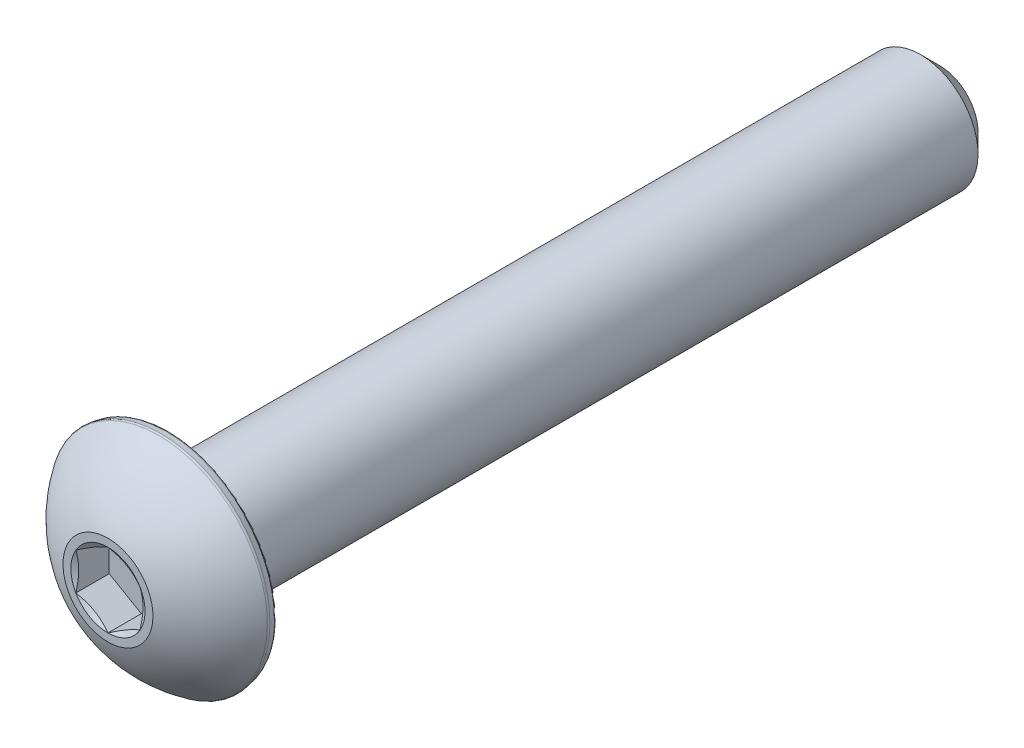
SolidWorks part; units mm, degrees
material "Cast Alloy Steel"
ref_plane "Front Plane" through (0, 0, 0) normal (0, 0, 1) x (1, 0, 0)
ref_plane "Top Plane" through (0, 0, 0) normal (0, 1, 0) x (1, 0, 0)
ref_plane "Right Plane" through (0, 0, 0) normal (1, 0, 0) x (0, 0, -1)
sketch "Sketch1" plane through (0, 0, 0) normal (1, 0, 0) x (0, 0, -1)
  line L0 (0, 0) -> (19.05, 0) construction
  line L1 (19.05, 1.4224) -> (19.05, -1.4224) construction
  line L2 (0, 0) -> (-1.4986, 0) construction
  line L3 (0, 2.7051) -> (0, -2.7051) construction
  line L4 (-1.4986, 0.7937) -> (-1.4986, -0.7937) construction
  line L5 (19.0103, 1.4911) -> (19.6453, 1.4911) construction
  line L6 (19.6453, 1.4911) -> (19.3278, 0.9412) construction
  line L7 (19.3278, 0.9412) -> (19.0103, 1.4911) construction
  line L8 (19.0302, 1.4568) -> (19.6255, 1.4568) construction
  line L9 (19.05, 1.4224) -> (19.6056, 1.4224) construction
  line L10 (19.2881, 1.01) -> (19.3675, 1.01) construction
  line L11 (19.3278, 1.01) -> (19.3278, 0.9412) construction
  line L12 (19.3278, 1.4224) -> (19.3278, 1.4911) construction
  point P5 (19.05, 0)
  point P10 (-1.4986, 0)
  point P13 (0, 0)
  point P18 (17.4625, -1.4224)
  point P25 (19.3278, 1.4568)
  dimension "Screw Size Decimal Equivalent" = 2.8448
  dimension "Length" = 19.05
  dimension "Head Diameter" = 5.4102
  dimension "Drive Size" = 1.5875
  dimension "Head Height" = 1.4986
  dimension "D1" = 60
  dimension "Pitch" = 0.635
  dimension "D2" = 0.0794
  dimension "D3" = 1.5875
sketch "Sketch2" plane through (0, 0, 0) normal (1, 0, 0) x (0, 0, -1)
  line L0 (19.05, 0) -> (-1.4986, 0)
  line L1 (-1.4986, 0) -> (-1.4986, 1.1112)
  line L2 (-1.4986, 0) -> (-1.4986, 2.7051) construction
  line L3 (-1.4986, 2.7051) -> (0, 2.7051) construction
  line L4 (0, 2.6655) -> (-0.2248, 2.7051)
  line L5 (0, 2.7051) -> (0, -2.7051) construction
  line L6 (0, 2.6655) -> (0, 1.4224)
  line L7 (0, 1.4224) -> (18.5737, 1.4224)
  line L8 (18.5737, 1.4224) -> (19.05, 0.9462)
  line L9 (19.05, 1.4224) -> (19.05, -1.4224) construction
  line L10 (19.05, 0.9462) -> (19.05, 0)
  line L11 (-1.4986, 0) -> (-1.4986, -1.1113) construction
  arc A0 (-0.2248, 2.7051) -> (-1.4986, 1.1112) centre (1.5259, 0) ccw
  dimension "D1" = 45
  dimension "D2" = 0.4763
  dimension "D3" = 10
  dimension "D4" = 0.2248
  dimension "D5" = 2.2225
revolve "Revolve1" add sketch "Sketch2" angle 360 about L0
sketch "Sketch3" plane through (0, 0, 1.4986) normal (0, 0, 1) x (1, 0, 0)
  line L1 (0, 0.9165) -> (-0.7938, 0.4583)
  line L2 (-0.7938, 0.4583) -> (-0.7938, -0.4583)
  line L3 (-0.7938, -0.4583) -> (0, -0.9165)
  line L4 (0, -0.9165) -> (0.7937, -0.4583)
  line L5 (0.7937, -0.4583) -> (0.7937, 0.4583)
  line L6 (0.7937, 0.4583) -> (0, 0.9165)
  circle A0 centre (0, 0) radius 0.7938 construction
extrude "Cut-Extrude1" cut sketch "Sketch3" against normal blind 0.8242
sketch "Sketch4" plane through (0, 0, 1.4986) normal (0, 0, 1) x (1, 0, 0)
  circle A0 centre (0, 0) radius 0.9165
extrude "Cut-Extrude2" cut sketch "Sketch4" against normal blind 0.8242 draft 60
fillet "Fillet1" radius 0.0749 2 edges at (0, 2.7051, 0.2248) (0, 2.6655, 0)
sketch "Sketch8" plane through (0, 0, 0) normal (0, 0, 1) x (1, 0, 0)
  circle A0 centre (0, 0) radius 2.7051 construction
  circle A1 centre (0, 0) radius 0.7937 construction
ref_plane "Plane1" [suppressed] through (0, 0, -0.2858) normal (0, 0, 1) x (1, 0, 0)
split "Split1" [suppressed] bodies to split 106
sketch "Sketch5" [suppressed] plane through (0, 0, 0) normal (1, 0, 0) x (0, 0, -1)
  line L0 (19.0302, 1.4568) -> (19.6255, 1.4568)
  line L1 (19.6255, 1.4568) -> (19.3675, 1.01)
  line L2 (19.3675, 1.01) -> (19.2881, 1.01)
  line L3 (19.2881, 1.01) -> (19.0302, 1.4568)
sketch "Sketch6" [suppressed] plane through (0, 0, -19.05) normal (0, 0, -1) x (-1, 0, 0)
  circle A0 centre (0, 0) radius 1.4224
curve "Helix/Spiral1" [suppressed] pitch 0.635 height 19.685 turns 31
sweep "Cut-Sweep1" [suppressed] cut profiles "Sketch5" path "Helix/Spiral1"
combine bodies "Combine1" [suppressed] operation type add bodies to combine 109 107
sketch "Sketch7" [suppressed] plane through (0, 0, -0.2858) normal (0, 0, 1) x (1, 0, 0)
  circle A0 centre (0, 0) radius 1.4224
extrude "Boss-Extrude1" [suppressed] add sketch "Sketch7" against normal blind 1.5875 draft 45
fillet "Fillet2" [suppressed] radius 0.0749
equation "\"D2@Sketch1\"=\"Pitch@Sketch1\"/8"
equation "\"D2@Sketch2\"=\"Pitch@Sketch1\"*.75"
equation "\"D4@Sketch2\"=\"Head Height@Sketch1\"*.15"
equation "\"D5@Sketch2\"=\"Drive Size@Sketch1\"*1.4"
equation "\"D1@Cut-Extrude1\"=\"Head Height@Sketch1\"*.55"
equation "\"D1@Cut-Extrude2\"=\"D1@Cut-Extrude1\""
equation "\"D1@Fillet1\"=\"Head Height@Sketch1\"*.05"
equation "\"D4@Helix/Spiral1\"=\"Pitch@Sketch1\""
equation "\"D3@Helix/Spiral1\"=\"Length@Sketch1\"+\"Pitch@Sketch1\""
equation "\"D3@Sketch1\"=\"Pitch@Sketch1\"*2.5"
equation "\"D1@Fillet2\"=\"D1@Fillet1\""
equation "\"D1@Plane1\"=\"Pitch@Sketch1\"*.45"
equation "\"D1@Boss-Extrude1\"=\"Pitch@Sketch1\"*2.5"
